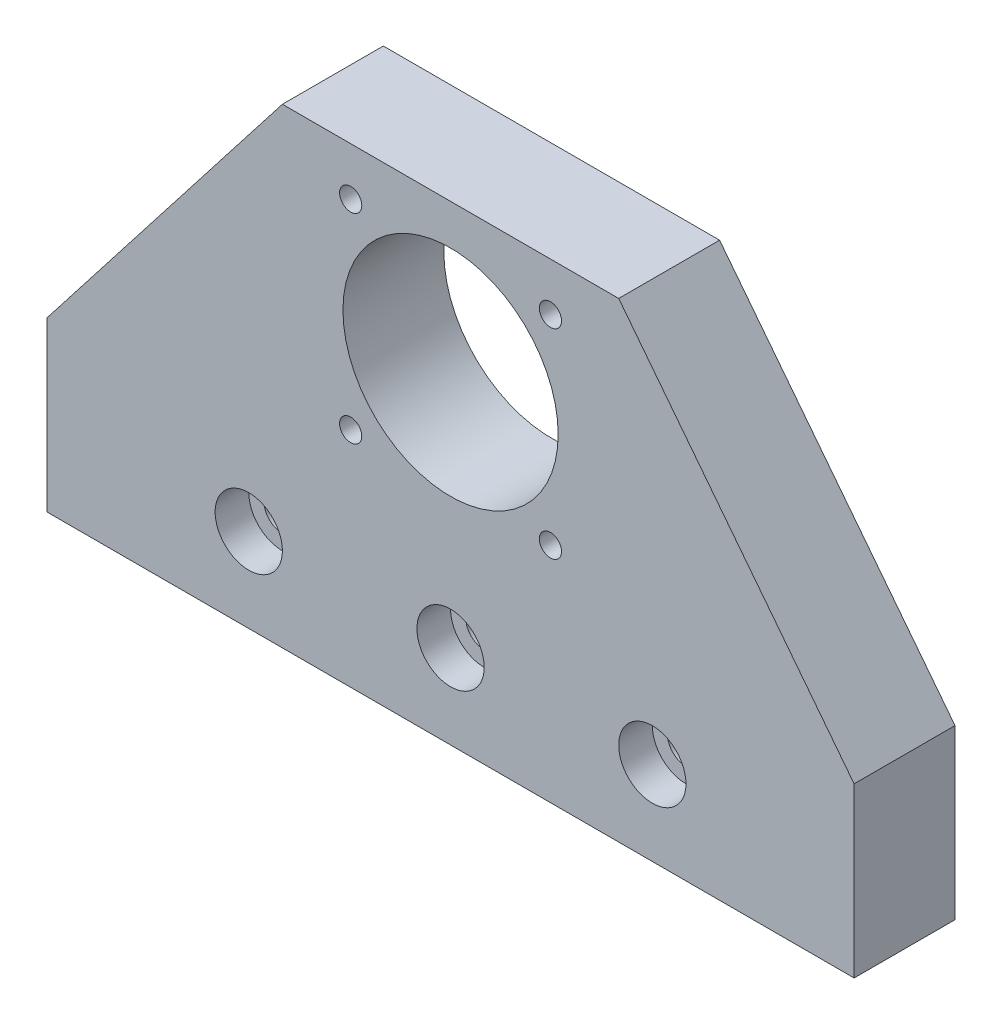
SolidWorks part; units mm, degrees
ref_plane "Front Plane" through (0, 0, 0) normal (0, 0, 1) x (1, 0, 0)
ref_plane "Top Plane" through (0, 0, 0) normal (0, 1, 0) x (1, 0, 0)
ref_plane "Right Plane" through (0, 0, 0) normal (1, 0, 0) x (0, 0, -1)
sketch "Sketch1" plane through (0, 0, 0) normal (0, 0, 1) x (1, 0, 0)
  line L0 (60, 0) -> (-60, 0)
  line L1 (-60, 0) -> (-60, 25)
  line L2 (-60, 25) -> (-25, 70)
  line L3 (-25, 70) -> (25, 70)
  line L4 (0, 0) -> (0, 70) construction
  line L5 (60, 25) -> (25, 70)
  line L6 (60, 0) -> (60, 25)
  dimension "D1" = 120
  dimension "D2" = 25
  dimension "D3" = 50
  dimension "D4" = 70
extrude "Boss-Extrude1" add sketch "Sketch1" along normal blind 15
sketch "Sketch2" plane through (0, 0, 15) normal (0, 0, 1) x (1, 0, 0)
  line L0 (0, 0) -> (0, 70) construction
  line L1 (-60, 0) -> (60, 0) construction
  line L2 (25, 70) -> (-25, 70) construction
  line L3 (-60, 12.5) -> (60, 12.5) construction
  line L4 (-60, 25) -> (-60, 0) construction
  line L5 (60, 0) -> (60, 25) construction
  point P12 (0, 12.5)
  point P13 (-30, 12.5)
  point P14 (30, 12.5)
  point P15 (0, 48)
  dimension "D1" = 30
hole_wizard "CBORE for M5 SHCS1" positions "3DSketch1" profile "Sketch3" counterbore size "M5" standard "ANSI Metric" end condition through all
sketch3d "3DSketch1"
  point P0 (-30, 12.5, 15)
  point P3 (0, 12.5, 15)
  point P6 (30, 12.5, 15)
sketch "Sketch3" plane through (-30, 12.5, 15) normal (1, 0, 0) x (0, -1, 0)
  line L0 (0, 0) -> (0, 15)
  line L1 (0, 15) -> (2.75, 15)
  line L3 (2.75, 15) -> (2.75, 5)
  line L4 (2.75, 5) -> (5, 5)
  line L5 (5, 5) -> (5, 0)
  line L7 (5, 0) -> (0, 0)
  line L11 (0, -6.35) -> (0, 107.95) construction
  dimension "Thru Hole Dia." = 5.5
  dimension "Thru Hole Depth" = 15
  dimension "C'Bore Dia." = 10
  dimension "C'Bore Depth" = 5
sketch "Sketch4" plane through (0, 0, 15) normal (0, 0, 1) x (1, 0, 0)
  circle A0 centre (0, 48) radius 16
  dimension "D1" = 32
extrude "Cut-Extrude1" cut sketch "Sketch4" against normal through all
sketch "Sketch5" plane through (0, 0, 15) normal (0, 0, 1) x (1, 0, 0)
  point P0 (14.8492, 33.1508)
  point P1 (-14.8492, 33.1508)
  point P2 (-14.8492, 62.8492)
  point P3 (14.8492, 62.8492)
hole_wizard "M4 Tapped Hole1" positions "3DSketch3" profile "Sketch7" tap size "M4" standard "ISO"
sketch3d "3DSketch3"
  point P0 (-14.8492, 62.8492, 15)
  point P3 (14.8492, 62.8492, 15)
  point P6 (14.8492, 33.1508, 15)
  point P9 (-14.8492, 33.1508, 15)
sketch "Sketch7" plane through (-14.8492, 62.8492, 15) normal (1, 0, 0) x (0, -1, 0)
  line L0 (0, 0) -> (0, 17.0914)
  line L1 (0, 17.0914) -> (1.65, 16.1)
  line L2 (1.65, 16.1) -> (1.65, 0)
  line L5 (1.65, 0) -> (0, 0)
  line L10 (0, 17.0914) -> (-1.65, 16.1) construction
  line L11 (0, -6.35) -> (0, 107.95) construction
  dimension "Tap Drill Dia." = 3.3
  dimension "Tap Drill Depth" = 16.1
  dimension "Drill Angle" = 118
